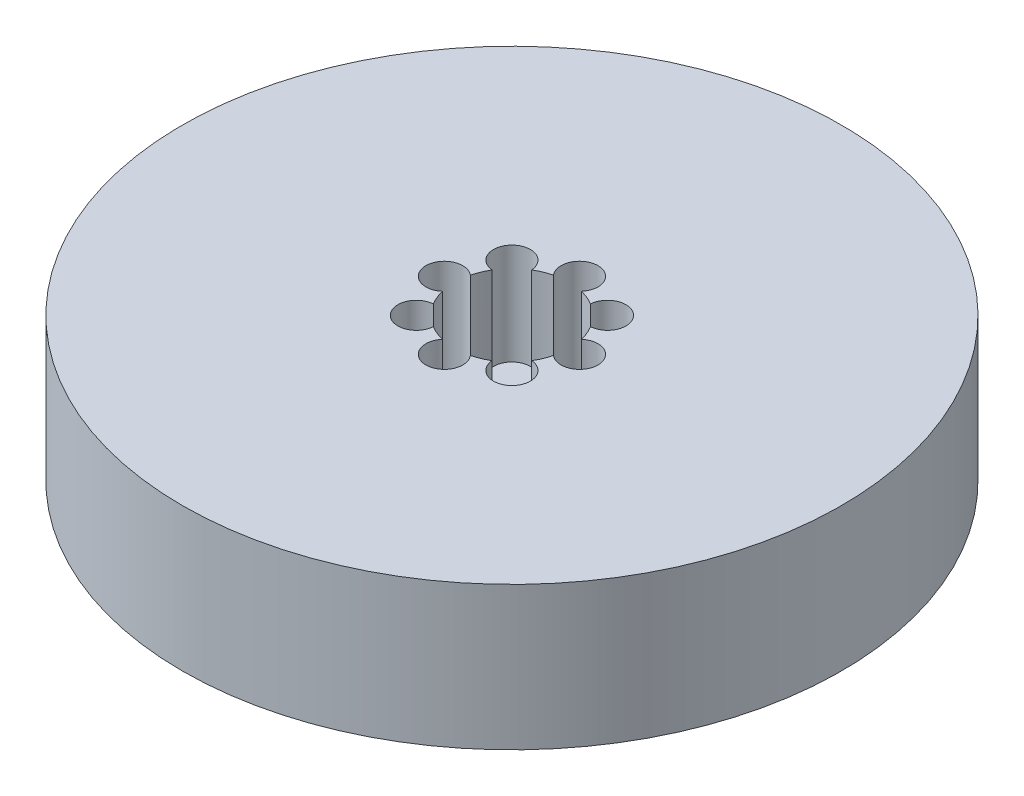
SolidWorks part; units mm, degrees
ref_plane "Front Plane" through (0, 0, 0) normal (0, 0, 1) x (1, 0, 0)
ref_plane "Top Plane" through (0, 0, 0) normal (0, 1, 0) x (1, 0, 0)
ref_plane "Right Plane" through (0, 0, 0) normal (1, 0, 0) x (0, 0, -1)
sketch "Sketch1" plane through (0, 0, 0) normal (0, 1, 0) x (1, 0, 0)
  circle A0 centre (0, 0) radius 57.5
  dimension "FLANGE_OD" = 115
extrude "Boss-Extrude1" add sketch "Sketch1" along normal blind 25
sketch "Sketch2" plane through (0, 0, 0) normal (0, 1, 0) x (1, 0, 0)
  circle A0 centre (0, 0) radius 10
  dimension "BORE_D" = 20
extrude "Cut-Extrude1" cut sketch "Sketch2" along normal through all
sketch "Sketch3" plane through (0, 25, 0) normal (0, 1, 0) x (1, 0, 0)
  circle A0 centre (0, 0) radius 11.7935 construction
  circle A1 centre (-11.7935, 0) radius 3.219
  dimension "BOLT_D" = 6.438
  dimension "BOLT_PCD" = 23.587
extrude "Cut-Extrude2" cut sketch "Sketch3" against normal blind 17.6696
pattern_circular "CirPattern1" count 8 over 360 about axis through (0, 0, 0) along (0, 1, 0) of "Cut-Extrude2"
